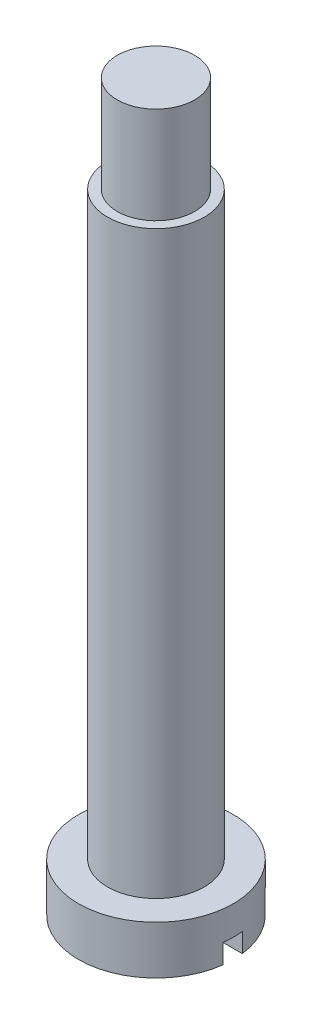
SolidWorks part; units mm, degrees
ref_plane "前视基准面" through (0, 0, 0) normal (0, 0, 1) x (1, 0, 0)
ref_plane "上视基准面" through (0, 0, 0) normal (0, 1, 0) x (1, 0, 0)
ref_plane "右视基准面" through (0, 0, 0) normal (1, 0, 0) x (0, 0, -1)
other "Configuration Table"
sketch "草图1" plane through (0, 0, 0) normal (0, 1, 0) x (1, 0, 0)
  circle A0 centre (0, 0) radius 4
  dimension "D1" = 8
extrude "凸台-拉伸1" add sketch "草图1" against normal blind 2.5
sketch "草图2" plane through (0, 0, 0) normal (0, 1, 0) x (1, 0, 0)
  circle A0 centre (0, 0) radius 2.5
  dimension "D1" = 5
extrude "凸台-拉伸2" add sketch "草图2" along normal blind 30 contours A0
sketch "草图3" plane through (0, 30, 0) normal (0, 1, 0) x (1, 0, 0)
  circle A0 centre (0, 0) radius 2
  dimension "D1" = 4
extrude "凸台-拉伸3" add sketch "草图3" along normal blind 5
sketch "草图4" plane through (0, -2.5, 0) normal (0, -1, 0) x (1, 0, 0)
  line L0 (-4, 0) -> (4, 0)
  circle A0 centre (0, 0) radius 4 construction
extrude "切除-拉伸-薄壁1" cut sketch "草图4" against normal blind 1 and the other way through all thin thin type mid plane wall 1
ref_axis "基准轴1" through (0, 39.9074, 0) along (0, -1, 0)
